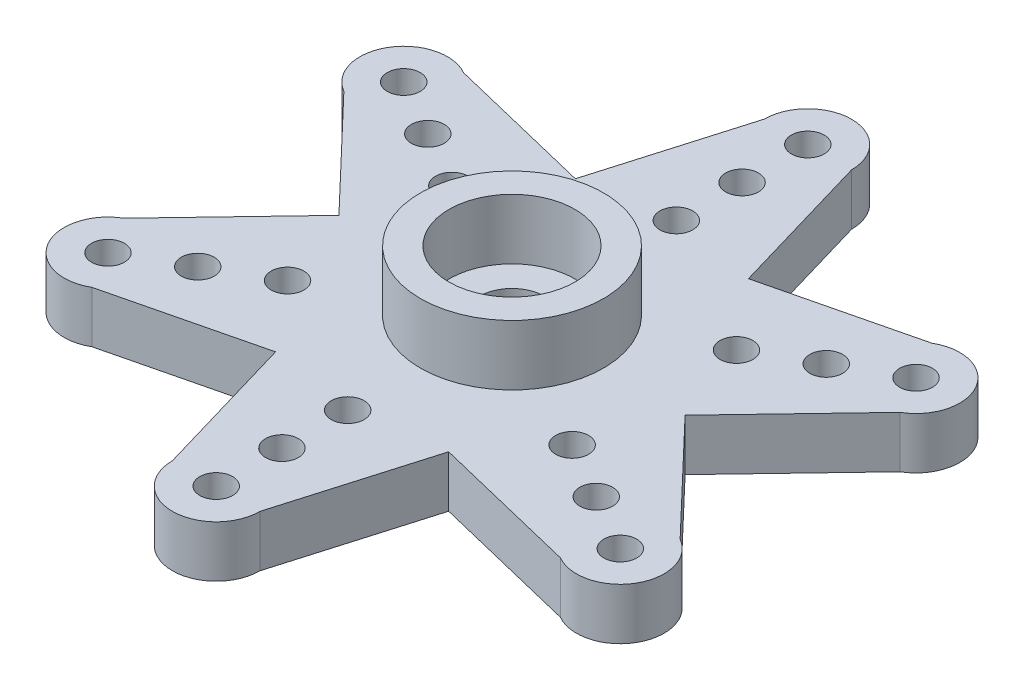
SolidWorks part; units mm, degrees
ref_plane "Front Plane" through (0, 0, 0) normal (0, 0, 1) x (1, 0, 0)
ref_plane "Top Plane" through (0, 0, 0) normal (0, 1, 0) x (1, 0, 0)
ref_plane "Right Plane" through (0, 0, 0) normal (1, 0, 0) x (0, 0, -1)
sketch "Sketch1" plane through (0, 0, 0) normal (0, 1, 0) x (1, 0, 0)
  line L0 (3.95, 6.8416) -> (10.6913, 8.4821)
  line L4 (-3.95, 6.8416) -> (-2, 13.5)
  line L5 (3.95, 6.8416) -> (2, 13.5)
  line L6 (7.9, 0) -> (12.6913, 5.0179)
  line L7 (7.9, 0) -> (12.6913, -5.0179)
  line L8 (3.95, -6.8416) -> (10.6913, -8.4821)
  line L9 (3.95, -6.8416) -> (2, -13.5)
  line L10 (-3.95, -6.8416) -> (-2, -13.5)
  line L11 (-3.95, -6.8416) -> (-10.6913, -8.4821)
  line L12 (-7.9, 0) -> (-12.6913, -5.0179)
  line L13 (-7.9, 0) -> (-12.6913, 5.0179)
  line L14 (-3.95, 6.8416) -> (-10.6913, 8.4821)
  line L15 (3.95, 6.8416) -> (10.6913, 8.4821)
  line L16 (7.9, 0) -> (12.6913, 5.0179)
  line L19 (7.9, 0) -> (12.6913, -5.0179)
  line L20 (3.95, -6.8416) -> (10.6913, -8.4821)
  line L23 (3.95, -6.8416) -> (2, -13.5)
  line L24 (-3.95, -6.8416) -> (-2, -13.5)
  line L27 (-3.95, -6.8416) -> (-10.6913, -8.4821)
  line L28 (-7.9, 0) -> (-12.6913, -5.0179)
  line L31 (-7.9, 0) -> (-12.6913, 5.0179)
  line L32 (-3.95, 6.8416) -> (-10.6913, 8.4821)
  circle A0 centre (0, 0) radius 15.5
  circle A1 centre (0, 10.5) radius 0.75
  arc A2 (10.6913, 8.4821) -> (12.6913, 5.0179) centre (11.6913, 6.75) cw
  arc A3 (-2, 13.5) -> (2, 13.5) centre (0, 13.5) cw
  arc A4 (12.6913, -5.0179) -> (10.6913, -8.4821) centre (11.6913, -6.75) cw
  arc A5 (2, -13.5) -> (-2, -13.5) centre (0, -13.5) cw
  arc A6 (-10.6913, -8.4821) -> (-12.6913, -5.0179) centre (-11.6913, -6.75) cw
  arc A7 (-12.6913, 5.0179) -> (-10.6913, 8.4821) centre (-11.6913, 6.75) cw
  arc A8 (10.6913, 8.4821) -> (12.6913, 5.0179) centre (11.6913, 6.75) cw
  arc A9 (12.6913, -5.0179) -> (10.6913, -8.4821) centre (11.6913, -6.75) cw
  arc A10 (2, -13.5) -> (-2, -13.5) centre (0, -13.5) cw
  arc A11 (-10.6913, -8.4821) -> (-12.6913, -5.0179) centre (-11.6913, -6.75) cw
  arc A12 (-12.6913, 5.0179) -> (-10.6913, 8.4821) centre (-11.6913, 6.75) cw
  circle A13 centre (0, 13.5) radius 0.75
  circle A14 centre (0, 7.5) radius 0.75
  circle A15 centre (11.6913, 6.75) radius 0.75
  circle A16 centre (9.0933, 5.25) radius 0.75
  circle A17 centre (6.4952, 3.75) radius 0.75
  circle A18 centre (11.6913, -6.75) radius 0.75
  circle A19 centre (9.0933, -5.25) radius 0.75
  circle A20 centre (6.4952, -3.75) radius 0.75
  circle A21 centre (0, -13.5) radius 0.75
  circle A22 centre (0, -10.5) radius 0.75
  circle A23 centre (0, -7.5) radius 0.75
  circle A24 centre (-11.6913, -6.75) radius 0.75
  circle A25 centre (-9.0933, -5.25) radius 0.75
  circle A26 centre (-6.4952, -3.75) radius 0.75
  circle A27 centre (-11.6913, 6.75) radius 0.75
  circle A28 centre (-9.0933, 5.25) radius 0.75
  circle A29 centre (-6.4952, 3.75) radius 0.75
  point P94 (0, 0)
  dimension "D1" = 6
  dimension "D2" = 6
extrude "Boss-Extrude1" add sketch "Sketch1" along normal blind 2.35 contours A7 L13 L12 A6 L11 L10 A5 L9 L8 A4 L7 L6 A2 L0 L5 A3 L4 L14 A29 A28 A27 A26 A25 A24 A23 A22 A21 A20 A19 A18 A17 region at (0, 0, 0)
sketch "Sketch2" plane through (0, 2.35, 0) normal (0, 1, 0) x (1, 0, 0)
  line L0 (-3.95, 6.8416) -> (3.95, -6.8416) construction
  line L1 (-7.9, 0) -> (7.9, 0) construction
  circle A0 centre (0, 0) radius 1.5
  circle A1 centre (0, 0) radius 2.5485
  circle A2 centre (0, 0) radius 4.18
extrude "Cut-Extrude1" cut sketch "Sketch2" against normal blind 2.35 contours A0 region at (0, 2.35, 0)
sketch "Sketch3" plane through (0, 2.35, 0) normal (0, 1, 0) x (1, 0, 0)
  circle A0 centre (0, 0) radius 2.875
  circle A1 centre (0, 0) radius 4.18
extrude "Boss-Extrude2" add sketch "Sketch3" along normal blind 2.75
